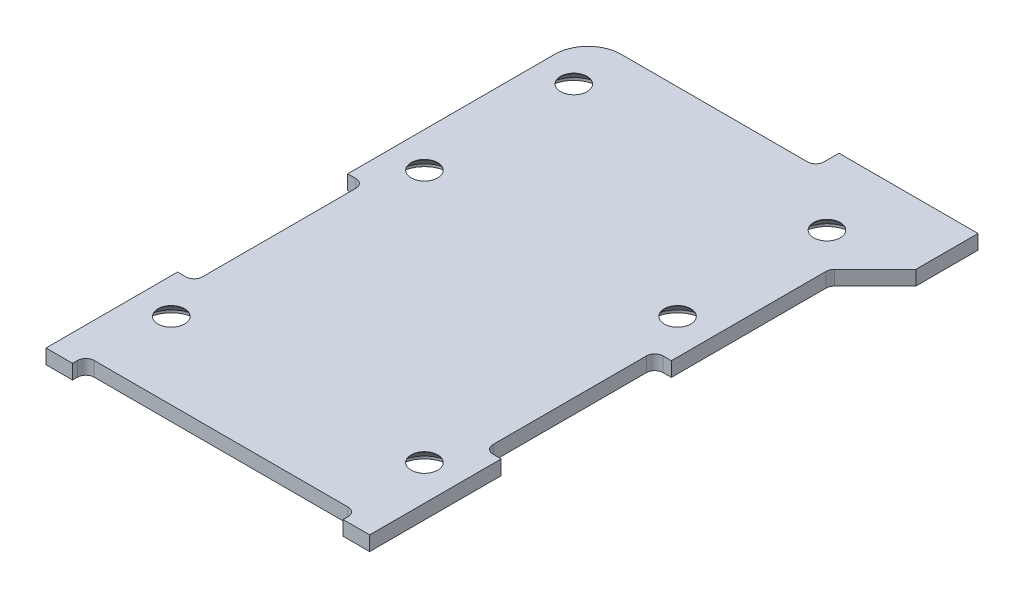
SolidWorks part; units mm, degrees
ref_plane "Front Plane" through (0, 0, 0) normal (0, 0, 1) x (1, 0, 0)
ref_plane "Top Plane" through (0, 0, 0) normal (0, 1, 0) x (1, 0, 0)
ref_plane "Right Plane" through (0, 0, 0) normal (1, 0, 0) x (0, 0, -1)
sketch "Sketch1" plane through (0, 0, 0) normal (0, 1, 0) x (1, 0, 0)
  line L1 (-18, 31.1) -> (18, 31.1)
  line L2 (-18, 31.1) -> (-18, -31.1)
  line L3 (-18, -31.1) -> (18, -31.1)
  line L4 (18, 31.1) -> (18, -31.1)
  line L5 (-18, 31.1) -> (18, -31.1) construction
  line L6 (-18, -31.1) -> (18, 31.1) construction
  point P0 (0, 0)
  dimension "D1" = 36
  dimension "D2" = 62.2
extrude "Base shape" add sketch "Sketch1" along normal blind 1.75
sketch "Sketch2" plane through (0, 1.75, 0) normal (0, 1, 0) x (1, 0, 0)
  line L0 (0, 31.1) -> (0, -31.1) construction
  line L1 (18, 31.1) -> (-18, 31.1) construction
  line L2 (-18, -31.1) -> (18, -31.1) construction
  line L4 (-18, 2.15) -> (-17.5, 2.15)
  line L5 (-18, 2.15) -> (-18, -18.35)
  line L6 (-18, -18.35) -> (-17.5, -18.35)
  line L7 (-17.5, 2.15) -> (-17.5, -18.35)
  line L8 (-17.5, -8.1) -> (-18, -8.1) construction
  line L9 (-15.25, -31.1) -> (-15.25, 31.1) construction
  line L11 (-18, -8.1) -> (18, -8.1) construction
  line L13 (15.25, 7.15) -> (15.25, -8.1) construction
  line L14 (15.25, 7.15) -> (0, 7.15) construction
  line L15 (18, -18.35) -> (17.5, -18.35)
  line L16 (17.5, 2.15) -> (17.5, -18.35)
  line L17 (18, 2.15) -> (17.5, 2.15)
  line L18 (18, 2.15) -> (18, -18.35)
  line L19 (18, -31.1) -> (18, 31.1) construction
  line L20 (-18, -31.1) -> (18, -31.1)
  line L21 (-18, -31.1) -> (-18, 14.9)
  line L22 (-18, 14.9) -> (18, 14.9)
  line L23 (18, -31.1) -> (18, 14.9)
  circle A0 centre (15.25, 7.15) radius 1.6
  circle A1 centre (15.25, -23.35) radius 1.6
  circle A2 centre (-15.25, 7.15) radius 1.6
  circle A3 centre (-15.25, -23.35) radius 1.6
  circle A4 centre (-15.25, 25.15) radius 1.6
  circle A5 centre (15.25, 25.15) radius 1.6
  line M13 (18, -31.1) -> (18, 31.1)
  line M15 (-18, 31.1) -> (-18, -31.1)
  dimension "D4" = 3.2
  dimension "D1" = 20.5
  dimension "D2" = 46
  dimension "D3" = 35
  dimension "D5" = 30.5
  dimension "D6" = 18
extrude "Cutouts" cut sketch "Sketch2" against normal up to next contours A2 | A0 | L17 L16 L15 M13 | L7 L4 L6 M15 | A3 | A1 | A4 | A5 region at (-17.75, 1.75, 8.1) region at (17.75, 1.75, 8.1) region at (15.25, 1.75, -7.15) region at (15.25, 1.75, 23.35) region at (-15.25, 1.75, -7.15) region at (-15.25, 1.75, 23.35)
sketch "Sketch3" plane through (0, 0, 0) normal (0, -1, 0) x (1, 0, 0)
  line L0 (18, -16.625) -> (19.5, -16.625) construction
  line L1 (19.5, 32.6) -> (-19.5, 32.6)
  line L2 (19.5, 32.6) -> (19.5, -32.6)
  line L3 (19.5, -32.6) -> (-19.5, -32.6)
  line L4 (-19.5, 32.6) -> (-19.5, -32.6)
  line L5 (19.5, 32.6) -> (-19.5, -32.6) construction
  line L6 (19.5, -32.6) -> (-19.5, 32.6) construction
  line L7 (0, -31.1) -> (0, -32.6) construction
  line L8 (-19.5, -31.1) -> (19.5, -31.1)
  line L9 (-19.5, -2.15) -> (19.5, -2.15)
  line L10 (-19.5, 18.35) -> (19.5, 18.35)
  line L11 (-19.5, 31.1) -> (19.5, 31.1)
  line L12 (-18, 18.35) -> (-17.5, 18.35)
  line L13 (-18, 31.1) -> (-18, 18.35)
  line L14 (18, 31.1) -> (-18, 31.1)
  line L15 (18, 18.35) -> (18, 31.1)
  line L16 (17.5, 18.35) -> (18, 18.35)
  line L17 (17.5, -2.15) -> (17.5, 18.35)
  line L18 (18, -2.15) -> (17.5, -2.15)
  line L19 (18, -31.1) -> (18, -2.15)
  line L20 (-18, -31.1) -> (18, -31.1)
  line L21 (-18, -2.15) -> (-18, -31.1)
  line L22 (-17.5, -2.15) -> (-18, -2.15)
  line L23 (-17.5, 18.35) -> (-17.5, -2.15)
  line L24 (-18, 18.35) -> (-17.5, 18.35)
  line L25 (-18, 31.1) -> (-18, 18.35)
  line L26 (18, 31.1) -> (-18, 31.1)
  line L27 (18, 18.35) -> (18, 31.1)
  line L28 (17.5, 18.35) -> (18, 18.35)
  line L29 (17.5, -2.15) -> (17.5, 18.35)
  line L30 (18, -2.15) -> (17.5, -2.15)
  line L31 (18, -31.1) -> (18, -2.15)
  line L32 (-18, -31.1) -> (18, -31.1)
  line L33 (-18, -2.15) -> (-18, -31.1)
  line L34 (-17.5, -2.15) -> (-18, -2.15)
  line L35 (-17.5, 18.35) -> (-17.5, -2.15)
  line L37 (24.7, -26.4) -> (24.7, -33.9) construction
  line L38 (7.95, -33.9) -> (24.7, -33.9) construction
  line L39 (7.95, -33.9) -> (7.95, -14.9) construction
  line L40 (24.7, -26.4) -> (19.5, -21.2) construction
  line L41 (24.7, -26.4) -> (24.7, -33.9)
  line L42 (7.95, -33.9) -> (24.7, -33.9)
  line L43 (7.95, -33.9) -> (7.95, -14.9)
  line L44 (24.7, -26.4) -> (19.5, -21.2)
  point P2 (0, 0)
  line M15 (18, -31.1) -> (18, -2.15)
  line M16 (18, 31.1) -> (-18, 31.1)
  line M17 (-18, 31.1) -> (-18, 18.35)
  line M35 (-18, -2.15) -> (-18, -31.1)
  line M36 (18, 18.35) -> (18, 31.1)
  dimension "D2" = 1.5
  dimension "D1" = 0
extrude "Extra size" add sketch "Sketch3" against normal up to surface (1.75 mm away) contours L9 L4 L8 M35 | L9 L8 L2 M15 | L11 L4 L10 M17 | L11 L10 L2 M36 | L4 L11 L2 L1 M16 | L43 L42 L41 L2 L3 | L43 L3 L2 L8 L32 region at (0, 0, 31.85) region at (18.75, 0, 24.725) region at (-18.75, 0, 24.725) region at (18.75, 0, -16.625) region at (-18.75, 0, -16.625) region at (20.0645, 0, -29.7415) region at (13.725, 0, -31.85) up to face at (15.25, 1.75, 24.95)
sketch "Sketch4" plane through (0, 0, 0) normal (0, 1, 0) x (1, 0, 0)
  circle A0 centre (-15.25, 25.15) radius 3
  circle A1 centre (15.25, 25.15) radius 3
  circle A2 centre (15.25, 7.15) radius 3
  circle A3 centre (-15.25, 7.15) radius 3
  circle A4 centre (-15.25, -23.35) radius 3
  circle A5 centre (15.25, -23.35) radius 3
  dimension "D1" = 6
extrude "Screw head cut" cut sketch "Sketch4" along normal blind 0.3
chamfer "Screw chamfer" distance 1.4 angle 45 6 edges at (-15.25, 0.3, 24.95) (15.25, 0.3, 24.95) (15.25, 0.3, -5.55) (15.25, 0.3, -23.55) (-15.25, 0.3, -23.55) (-15.25, 0.3, -5.55)
fillet "Front fillets" radius 4 1 edges at (-19.5, 0.875, -31.1)
sketch "Sketch6" plane through (0, 0, 32.6) normal (0, 0, 1) x (1, 0, 0)
  line L0 (19.5, 0) -> (-19.5, 0) construction
  line L1 (19.5, 1.75) -> (16.3, 1.75)
  line L2 (19.5, 1.75) -> (19.5, 0)
  line L3 (19.5, 0) -> (16.3, 0)
  line L4 (16.3, 1.75) -> (16.3, 0)
  line L7 (-19.5, 0) -> (-16.3, 0)
  line L8 (-19.5, 0) -> (-19.5, 1.75)
  line L9 (-19.5, 1.75) -> (-16.3, 1.75)
  line L10 (-16.3, 0) -> (-16.3, 1.75)
  line L11 (19.5, 1.75) -> (-19.5, 1.75) construction
  line L14 (16.3, 9.95) -> (16.3, 1.75) construction
  line L15 (-16.3, 1.75) -> (-16.3, 9.95) construction
extrude "Ledbar sides" add sketch "Sketch6" along normal up to surface (1.6 mm away)
fillet "Milling fillets" radius 1 8 edges at (-16.3, 0.875, 32.6) (16.3, 0.875, 32.6) (17.5, 0.875, -2.15) (17.5, 0.875, 18.35) (-17.5, 0.875, -2.15) (-17.5, 0.875, 18.35) (19.5, 0.875, -21.2) (7.95, 0.875, -31.1)
